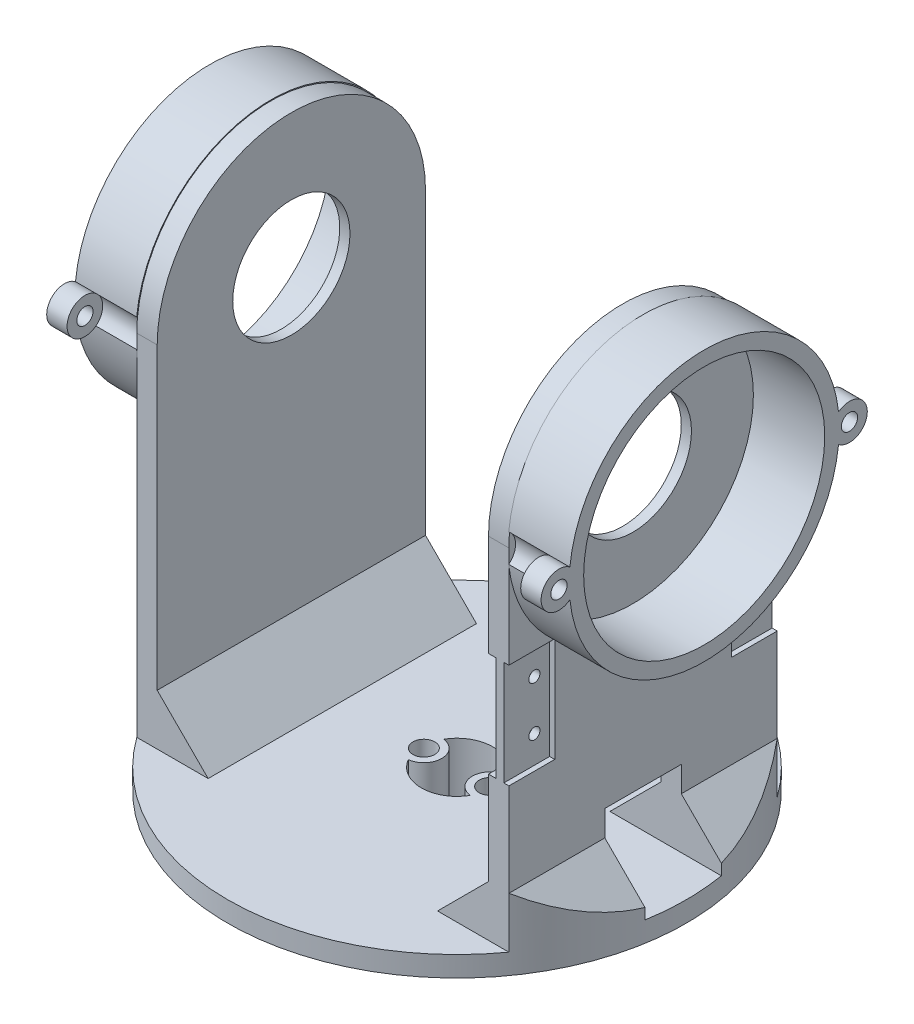
SolidWorks part; units mm, degrees
material "PLA"
ref_plane "Front Plane" through (0, 0, 0) normal (0, 0, 1) x (1, 0, 0)
ref_plane "Top Plane" through (0, 0, 0) normal (0, 1, 0) x (1, 0, 0)
ref_plane "Right Plane" through (0, 0, 0) normal (1, 0, 0) x (0, 0, -1)
sketch "Sketch1" plane through (0, 0, 0) normal (0, 1, 0) x (1, 0, 0)
  line L0 (-44.5982, 6) -> (-49, 0)
  line L1 (-49, 0) -> (-44.5982, -6)
  line L2 (0, 0) -> (-49, 0) construction
  arc A0 (-44.5982, -6) -> (-44.5982, 6) centre (0, 0) ccw
  dimension "D1" = 90
  dimension "D2" = 4
  dimension "D3" = 6
extrude "Boss-Extrude1" add sketch "Sketch1" along normal mid plane 4
fillet "Fillet1" radius 2 1 edges at (-49, 0, 0)
sketch "Sketch2" plane through (0, 2, 0) normal (0, 1, 0) x (1, 0, 0)
  line L0 (-36.5, 26.3201) -> (-36.5, -26.3201)
  line L1 (-32.5, 26.3201) -> (-32.5, -31.1247)
  line L2 (0, 45) -> (0, -45) construction
  line L3 (32.5, 26.3201) -> (32.5, -26.3201)
  line L4 (36.5, 26.3201) -> (36.5, -26.3201)
  line L5 (-36.5, 26.3201) -> (-32.5, 26.3201)
  line L6 (-36.5, -26.3201) -> (-32.5, -26.3201)
  line L7 (36.5, 26.3201) -> (32.5, 26.3201)
  line L8 (36.5, -26.3201) -> (32.5, -26.3201)
  circle A0 centre (0, 0) radius 45 construction
  circle A1 centre (0, 0) radius 45
  arc M5 (-44.5982, -6) -> (-44.5982, 6) centre (0, 0) ccw
  dimension "D1" = 4
  dimension "D2" = 32.5
  dimension "D3" = 4
extrude "Boss-Extrude2" add sketch "Sketch2" along normal blind 95 contours L1 L0 M5 | L4 L3 M5
sketch "Sketch3" plane through (0, 0, 0) normal (1, 0, 0) x (0, 0, -1)
  line L2 (26.3201, 97) -> (-26.3201, 97) construction
  line L3 (-26.3201, 70.6799) -> (-26.3201, 97)
  line L4 (-26.3201, 97) -> (26.3201, 97)
  line L5 (26.3201, 97) -> (26.3201, 70.6799)
  line L6 (-26.3201, 97) -> (-26.3201, 2) construction
  line L7 (26.3201, 97) -> (26.3201, 2) construction
  line L8 (26.3201, 97) -> (-26.3201, 97) construction
  arc A0 (-26.3201, 70.6799) -> (26.3201, 70.6799) centre (0, 70.6799) cw
extrude "Cut-Extrude1" cut sketch "Sketch3" against normal through all both and the other way through all contours L4 A0 L5 | L3 A0 L4
sketch "Sketch5" plane through (-36.5, 0, 0) normal (-1, 0, 0) x (0, 0, 1)
  circle A0 centre (0, 70.6799) radius 23.65
  dimension "D1" = 47.3
extrude "Bearing Indent" cut sketch "Sketch5" against normal blind 2
sketch "Sketch6" plane through (-36.5, 0, 0) normal (-1, 0, 0) x (0, 0, 1)
  circle A0 centre (0, 70.6799) radius 23.65 construction
  circle A1 centre (0, 70.6799) radius 23.65
  circle A2 centre (0, 70.6799) radius 26.5
  dimension "D1" = 53
extrude "Bearing Extrude" add sketch "Sketch6" along normal blind 12
sketch "Sketch7" plane through (-34.5, 0, 0) normal (-1, 0, 0) x (0, 0, 1)
  circle A0 centre (0, 70.6799) radius 11.5
  dimension "D1" = 23
extrude "Bearing Thru" cut sketch "Sketch7" against normal up to next
mirror "Bearing Mirror" about plane through (0, 0, 0) normal (1, 0, 0) of "Bearing Indent", "Bearing Thru", "Bearing Extrude"
sketch "Sketch8" plane through (0, -2, 0) normal (0, -1, 0) x (-1, 0, 0)
  circle A0 centre (0, 0) radius 10
  dimension "D1" = 20
extrude "Boss-Extrude4" add sketch "Sketch8" along normal blind 16.8
sketch "Sketch9" plane through (-36.5, 0, 0) normal (-1, 0, 0) x (0, 0, 1)
  circle A0 centre (-28.5, 70.6799) radius 3.5
  circle A1 centre (28.5, 70.6799) radius 3.5
  circle A3 centre (0, 70.6799) radius 11.5 construction
  circle A4 centre (0, 70.6799) radius 26.5 construction
  circle A6 centre (0, 70.6799) radius 11.5 construction
  dimension "D1" = 7
  dimension "D2" = 1.5
  dimension "D3" = 1.5
extrude "Boss-Extrude5" add sketch "Sketch9" along normal up to surface (12 mm away) up to face at (-48.5, 70.6799, 26.5)
sketch "Sketch12" plane through (36.5, 0, 0) normal (1, 0, 0) x (0, 0, -1)
  circle A0 centre (28.5, 70.6799) radius 3.5 construction
  circle A1 centre (-28.5, 70.6799) radius 3.5 construction
  circle A2 centre (28.5, 70.6799) radius 3.5
  circle A3 centre (-28.5, 70.6799) radius 3.5
extrude "Boss-Extrude6" add sketch "Sketch12" along normal up to surface (12 mm away) up to face at (48.5, 70.6799, 23.65)
sketch "Sketch15" plane through (0, -18.8, 0) normal (0, -1, 0) x (1, 0, 0)
  circle A2 centre (0, 0) radius 7
  circle A3 centre (0, 0) radius 7
  dimension "D1" = 3
extrude "Cut-Extrude2" cut sketch "Sketch15" against normal up to next
sketch "Sketch16" plane through (0, -18.8, 0) normal (0, -1, 0) x (1, 0, 0)
  circle A0 centre (-6.5, 0) radius 3.5
  circle A1 centre (6.5, 0) radius 3.5
  circle A2 centre (0, 0) radius 10 construction
  circle A3 centre (0, 0) radius 10 construction
  dimension "D1" = 7
extrude "Boss-Extrude7" add sketch "Sketch16" against normal up to surface (20.8 mm away) up to face at (0, 2, 7)
hole_wizard "M4 Clearance Hole1" positions "Sketch17" profile "Sketch18" hole size "M4" standard "ANSI Metric" end condition up to next
sketch "Sketch17" plane through (0, -18.8, 0) normal (0, -1, 0) x (-1, 0, 0)
  point P0 (6.5, 0)
  point P3 (-6.5, 0)
sketch "Sketch18" plane through (-6.5, -18.8, 0) normal (1, 0, 0) x (0, 0, -1)
  line L0 (0, 0) -> (0, 20.8)
  line L1 (0, 20.8) -> (2.15, 20.8)
  line L2 (2.15, 20.8) -> (2.15, 0)
  line L5 (2.15, 0) -> (0, 0)
  line L11 (0, -6.35) -> (0, 107.95) construction
  dimension "Thru Hole Dia." = 4.3
  dimension "Thru Hole Depth" = 20.8
sketch "Sketch20" plane through (36.5, 0, 0) normal (1, 0, 0) x (0, 0, -1)
  line L0 (26.3201, 2) -> (-26.3201, 2) construction
  line L1 (-7.5, 2) -> (7.5, 2)
  line L2 (-7.5, 2) -> (-7.5, 17)
  line L3 (-7.5, 17) -> (7.5, 17)
  line L4 (7.5, 2) -> (7.5, 17)
  point P6 (0, 17)
  dimension "D1" = 15
  dimension "D2" = 15
extrude "Cut-Extrude3" cut sketch "Sketch20" against normal up to next
sketch "Sketch21" plane through (36.5, 0, 0) normal (-1, 0, 0) x (0, 0, 1)
  circle A0 centre (-28.5, 70.6799) radius 3.5 construction
  circle A1 centre (-28.5, 70.6799) radius 3.5
  circle A2 centre (28.5, 70.6799) radius 3.5 construction
  circle A3 centre (28.5, 70.6799) radius 3.5
extrude "Cut-Extrude4" cut sketch "Sketch21" against normal offset from surface (8 mm away) 4 up to face at (48.5, 70.6799, 23.65)
hole_wizard "M3 Clearance Hole1" positions "Sketch13" profile "Sketch14" hole size "M3" standard "ANSI Metric"
sketch "Sketch13" plane through (48.5, 0, 0) normal (1, 0, 0) x (0, 0, -1)
  point P0 (-28.5, 70.6799)
  point P3 (28.5, 70.6799)
sketch "Sketch14" plane through (48.5, 70.6799, 28.5) normal (0, 1, 0) x (0, 0, -1)
  line L0 (0, 0) -> (0, 4)
  line L1 (0, 4) -> (1.6, 4)
  line L2 (1.6, 4) -> (1.6, 0)
  line L5 (1.6, 0) -> (0, 0)
  line L11 (0, -6.35) -> (0, 107.95) construction
  dimension "Thru Hole Dia." = 3.2
  dimension "Thru Hole Depth" = 4
sketch "Sketch22" plane through (-36.5, 0, 0) normal (1, 0, 0) x (0, 0, -1)
  circle A0 centre (28.5, 70.6799) radius 3.5 construction
  circle A1 centre (-28.5, 70.6799) radius 3.5 construction
  circle A2 centre (28.5, 70.6799) radius 3.5
  circle A3 centre (-28.5, 70.6799) radius 3.5
extrude "Cut-Extrude5" cut sketch "Sketch22" against normal offset from surface (8 mm away) 4 up to face at (-48.5, 70.6799, 0)
hole_wizard "M3 Clearance Hole2" positions "Sketch10" profile "Sketch11" hole size "M3" standard "ANSI Metric" end condition up to next
sketch "Sketch10" plane through (-48.5, 0, 0) normal (-1, 0, 0) x (0, 0, 1)
  point P0 (-28.5, 70.6799)
  point P3 (28.5, 70.6799)
sketch "Sketch11" plane through (-48.5, 70.6799, -28.5) normal (0, 1, 0) x (0, 0, 1)
  line L0 (0, 0) -> (0, 4)
  line L1 (0, 4) -> (1.6, 4)
  line L2 (1.6, 4) -> (1.6, 0)
  line L5 (1.6, 0) -> (0, 0)
  line L11 (0, -6.35) -> (0, 107.95) construction
  dimension "Thru Hole Dia." = 3.2
  dimension "Thru Hole Depth" = 4
sketch "Sketch24" plane through (36.5, 0, 0) normal (1, 0, 0) x (0, 0, -1)
  line L0 (26.3201, 67.5976) -> (26.3201, 2) construction
  line L1 (26.3201, 50.75) -> (17.3201, 50.75)
  line L2 (26.3201, 50.75) -> (26.3201, 30.25)
  line L3 (26.3201, 30.25) -> (17.3201, 30.25)
  line L4 (17.3201, 50.75) -> (17.3201, 30.25)
  line L5 (-26.3201, 67.5976) -> (-26.3201, 2) construction
  line L6 (-26.3201, 50.75) -> (-17.3201, 50.75)
  line L7 (-26.3201, 50.75) -> (-26.3201, 30.25)
  line L8 (-26.3201, 30.25) -> (-17.3201, 30.25)
  line L9 (-17.3201, 50.75) -> (-17.3201, 30.25)
  line L10 (-17.3201, 40.5) -> (-26.3201, 40.5) construction
  line L11 (-7.5, 2) -> (-26.3201, 2) construction
  dimension "D1" = 20.5
  dimension "D2" = 38.5
  dimension "D3" = 9
extrude "Cut-Extrude6" cut sketch "Sketch24" against normal offset from surface (1 mm away) 3 up to face at (32.5, 70.6799, -11.5)
hole_wizard "M2 Clearance Hole2" positions "Sketch26" profile "Sketch27" hole size "M2" standard "ANSI Metric"
sketch "Sketch26" plane through (35.5, 0, 0) normal (1, 0, 0) x (0, 0, -1)
  line L0 (20.3201, 45.345) -> (20.3201, 35.655) construction
  line L2 (-20.3201, 45.345) -> (-20.3201, 35.655) construction
  line L4 (-17.3201, 50.75) -> (-17.3201, 30.25) construction
  line L5 (-20.3201, 40.5) -> (-17.3201, 40.5) construction
  line L7 (17.3201, 50.6234) -> (17.3201, 30.25) construction
  point P0 (-20.3201, 45.345)
  point P2 (-20.3201, 35.655)
  point P4 (20.3201, 45.345)
  point P6 (20.3201, 35.655)
  dimension "D1" = 9.69
  dimension "D2" = 3
  dimension "D3" = 3
sketch "Sketch27" plane through (35.5, 45.345, 20.3201) normal (0, 1, 0) x (0, 0, -1)
  line L0 (0, 0) -> (0, 3)
  line L1 (0, 3) -> (1.1, 3)
  line L2 (1.1, 3) -> (1.1, 0)
  line L5 (1.1, 0) -> (0, 0)
  line L11 (0, -6.35) -> (0, 107.95) construction
  dimension "Thru Hole Dia." = 2.2
  dimension "Thru Hole Depth" = 3
chamfer "Chamfer1" distance 10 angle 45 6 edges at (-36.5, 2, 0) (-32.5, 2, 0) (36.5, 2, 16.9101) (32.5, 2, 16.9101) (32.5, 2, -16.9101) (36.5, 2, -16.9101)
sketch "Sketch28" plane through (32.5, 0, 0) normal (-1, 0, 0) x (0, 0, 1)
  line L0 (26.3201, 50.75) -> (26.3201, 30.25) construction
  line L1 (26.3201, 30.25) -> (17.3201, 30.25) construction
  line L2 (17.3201, 30.25) -> (17.3201, 50.75) construction
  line L3 (17.3201, 50.75) -> (26.3201, 50.75) construction
  line L4 (-26.3201, 30.25) -> (-26.3201, 50.75) construction
  line L5 (-26.3201, 50.75) -> (-17.3201, 50.75) construction
  line L6 (-17.3201, 50.75) -> (-17.3201, 30.25) construction
  line L7 (-17.3201, 30.25) -> (-26.3201, 30.25) construction
  line L8 (26.3201, 50.75) -> (26.3201, 30.25)
  line L9 (26.3201, 30.25) -> (17.3201, 30.25)
  line L10 (17.3201, 30.25) -> (17.3201, 50.75)
  line L11 (17.3201, 50.75) -> (26.3201, 50.75)
  line L12 (-26.3201, 30.25) -> (-26.3201, 50.75)
  line L13 (-26.3201, 50.75) -> (-17.3201, 50.75)
  line L14 (-17.3201, 50.75) -> (-17.3201, 30.25)
  line L15 (-17.3201, 30.25) -> (-26.3201, 30.25)
  circle A0 centre (-20.3201, 35.655) radius 1.1 construction
  circle A1 centre (-20.3201, 45.345) radius 1.1 construction
  circle A2 centre (20.3201, 35.655) radius 1.1 construction
  circle A3 centre (20.3201, 45.345) radius 1.1 construction
  circle A4 centre (-20.3201, 35.655) radius 1.1
  circle A5 centre (-20.3201, 45.345) radius 1.1
  circle A6 centre (20.3201, 35.655) radius 1.1
  circle A7 centre (20.3201, 45.345) radius 1.1
extrude "Cut-Extrude7" cut sketch "Sketch28" against normal offset from surface (1.5 mm away) 1.5 up to face at (35.5, 45.345, -21.4201)
equation "\"D3@Sketch9\"=\"D2@Sketch9\""
equation "\"D3@Sketch2\"=\"D1@Sketch2\""
equation "\"D3@Sketch26\"=\"D2@Sketch26\""
